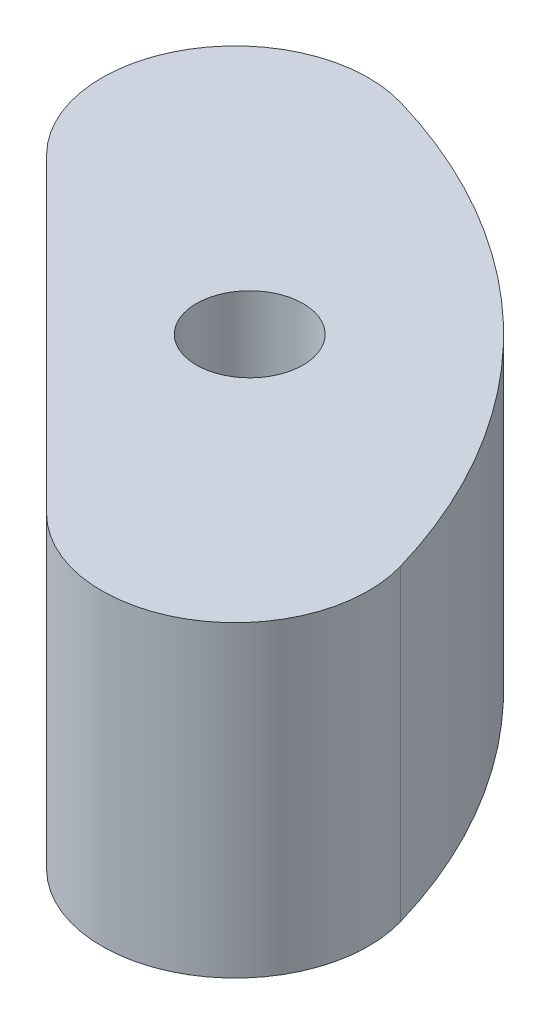
SolidWorks part; units mm, degrees
ref_plane "Front Plane" through (0, 0, 0) normal (0, 0, 1) x (1, 0, 0)
ref_plane "Top Plane" through (0, 0, 0) normal (0, 1, 0) x (1, 0, 0)
ref_plane "Right Plane" through (0, 0, 0) normal (1, 0, 0) x (0, 0, -1)
sketch "Sketch2" plane through (0, 0, 0) normal (0, 1, 0) x (1, 0, 0)
  line L1 (-17.9605, -17.9605) -> (17.9605, -17.9605) construction
  line L2 (-17.9605, -17.9605) -> (-17.9605, 17.9605) construction
  line L3 (-17.9605, 17.9605) -> (17.9605, 17.9605) construction
  line L4 (17.9605, -17.9605) -> (17.9605, 17.9605) construction
  line L5 (-17.9605, -17.9605) -> (17.9605, 17.9605) construction
  line L6 (-17.9605, 17.9605) -> (17.9605, -17.9605) construction
  line L7 (-11.3537, 34.7024) -> (34.7024, -11.3537)
  arc A1 (34.7024, -11.3537) -> (-11.3537, 34.7024) centre (0, 0) ccw
  circle A3 centre (17.9605, 17.9605) radius 3.302
  arc A4 (-11.3537, 34.7024) -> (34.7024, -11.3537) centre (0, 0) ccw construction
  dimension "D1" = 73.025
  dimension "D4" = 6.604
  dimension "D2" = 50.8
  dimension "D3" = 8.89
extrude "Boss-Extrude2" add sketch "Sketch2" along normal mid plane 19.05
sketch "Sketch4" plane through (11.6743, 0, -11.6743) normal (-0.7071, 0, 0.7071) x (0.7071, 0, 0.7071)
  line L1 (-9.97, 6.25) -> (9.97, 6.25) construction
  line L2 (-9.97, 6.25) -> (-9.97, -6.25) construction
  line L3 (-9.97, -6.25) -> (9.97, -6.25) construction
  line L4 (9.97, 6.25) -> (9.97, -6.25) construction
  line L5 (-9.97, 6.25) -> (9.97, -6.25) construction
  line L6 (-9.97, -6.25) -> (9.97, 6.25) construction
  circle A0 centre (9.97, 6.25) radius 1.95
  circle A1 centre (-9.97, 6.25) radius 1.95
  circle A2 centre (-9.97, -6.25) radius 1.95
  circle A3 centre (9.97, -6.25) radius 1.95
  point P0 (0, 0)
  dimension "D1" = 3.9
  dimension "D2" = 19.94
  dimension "D3" = 12.5
extrude "Cut-Extrude2" cut sketch "Sketch4" against normal blind 5.8
fillet "Fillet1" radius 8.255 2 edges at (34.7024, 0, 11.3537) (-11.3537, 0, -34.7024)
equation "\"AIRFRAME_OD\"= 3.091in"
equation "\"AIRFRAME_ID\"= 3.00in"
equation "\"FLAT_T\"= 0.125in"
equation "\"NOSE_EXP_L\"= 3.5in"
equation "\"NOSE_SHOULDER_L\"= 5in"
equation "\"MAIN_L\"= 30in"
equation "\"RECO_COUP_L\"= 6in"
equation "\"RECO_SWITCH_L\"= 1.5in"
equation "\"DROGUE_L\"= 14in"
equation "\"ATS_FORE_COUP_L\"= 4in"
equation "\"ATS_AFT_COUP_L\"= 2.5in"
equation "\"LOWER_L\"= 16in"
equation "\"FIN_N\"= 4"
equation "\"CR_AFT_X\"= 0.5in"
equation "\"CR_FORE_X\"= 6in"
equation "\"COUPLER_OD\"= 2.998in"
equation "\"COUPLER_ID\"= 2.875in"
equation "\"RECO_ROD_X\"= 1.5in"
equation "\"ATS_ROD_X\"= 2in"
equation "\"FIN_ROOT\"= 5in"
equation "\"FIN_X\"= 0.75in"
equation "\"MOTOR_OD\"= 2.25in"
equation "\"MOTOR_ID\"= 2.126in"
equation "\"MOTOR_L\"= 8in"
equation "\"MOTOR_LOWER_X\"= 0.5in"
equation "\"NOSE_CONE_L\"=14.5in"
equation "\"ATS_LIPO_L\"= 1.92in"
equation "\"ATS_LIPO_W\"= 0.42in"
equation "\"ATS_LIPO_H\"= 0.94in "
equation "\"ATS_STANDOFF_H\"= 10mm"
equation "\"ATS_STANDOFF_OD\"= 5.2mm"
equation "\"ATS_PCB_L\"= 2.5in"
equation "\"ATS_PCB_W\"= 1.45in"
equation "\"ATS_PCB_H\"= 1.2in"
equation "\"ATS_PCB_HOLESEP_W\"= 1.33in - 0.0985in"
equation "\"ATS_ALTI_L\"= 1.05in"
equation "\"ATS_ALTI_W\"= 0.7in"
equation "\"ATS_ALTI_H\"= 0.4in"
equation "\"D1@Sketch2\"=\"COUPLER_ID\""
